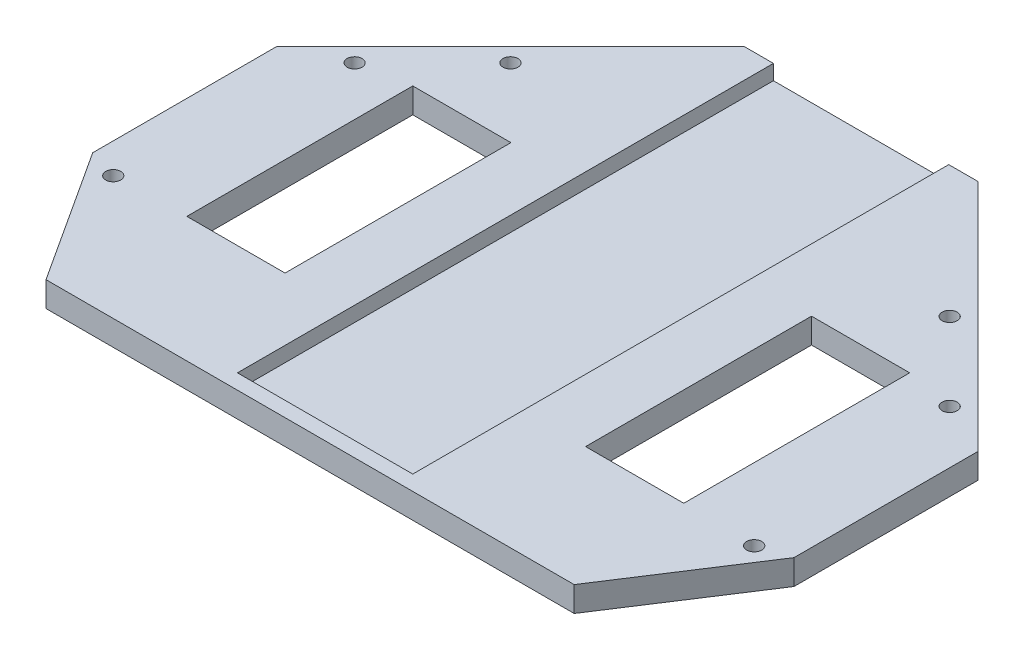
SolidWorks part; units mm, degrees
ref_plane "Front Plane" through (0, 0, 0) normal (0, 0, 1) x (1, 0, 0)
ref_plane "Top Plane" through (0, 0, 0) normal (0, 1, 0) x (1, 0, 0)
ref_plane "Right Plane" through (0, 0, 0) normal (1, 0, 0) x (0, 0, -1)
sketch "Sketch1" plane through (0, 0, 0) normal (0, 1, 0) x (1, 0, 0)
  line L0 (-52.7197, -40) -> (-70, -13.3906)
  line L1 (-70, -13.3906) -> (-70, 23.3381)
  line L2 (-70, 23.3381) -> (-23.3381, 70)
  line L4 (0, -40) -> (0, 70)
  line L5 (0, -40) -> (-52.7197, -40)
  line L6 (-59.397, 28.2843) -> (-43.8406, 43.8406) construction
  line L7 (-51.9976, -33.7676) -> (-63.9796, -15.3169) construction
  line L8 (-23.3381, 70) -> (0, 70)
  line L9 (0, 0) -> (-85, 0) construction
  line L10 (-43.8406, 43.8406) -> (0, 0) construction
  line L11 (-51.9976, -33.7676) -> (0, 0) construction
  line L12 (-49.6, 30.1) -> (-30, 30.1)
  line L13 (-49.6, 30.1) -> (-49.6, -15)
  line L14 (-49.6, -15) -> (-30, -15)
  line L15 (-30, 30.1) -> (-30, -15)
  circle A0 centre (0, 0) radius 85 construction
  circle A1 centre (-43.8406, 43.8406) radius 1.5
  circle A2 centre (-59.397, 28.2843) radius 1.5
  circle A4 centre (-63.9796, -15.3169) radius 1.5
  dimension "D7" = 3
  dimension "D17" = 170
  dimension "D3" = 4
  dimension "D5" = 40
  dimension "D6" = 70
  dimension "D8" = 62
  dimension "D9" = 22
  dimension "D10" = 22
  dimension "D11" = 19.6
  dimension "D12" = 45.1
  dimension "D13" = 30
  dimension "D14" = 45
  dimension "D15" = 33
  dimension "D16" = 15
  dimension "D18" = 4
  dimension "D19" = 70
extrude "Boss-Extrude1" add sketch "Sketch1" along normal blind 5
mirror "Mirror1" about plane through (0, 5, 40) normal (-1, 0, 0) of "Boss-Extrude1"
sketch "Sketch2" plane through (0, 5, 0) normal (0, 1, 0) x (1, 0, 0)
  line L0 (23.3381, 70) -> (-23.3381, 70) construction
  line L1 (-17.5, 70) -> (17.5, 70)
  line L2 (-17.5, 70) -> (-17.5, -37)
  line L3 (-17.5, -37) -> (17.5, -37)
  line L4 (17.5, 70) -> (17.5, -37)
  line L5 (-52.7197, -40) -> (52.7197, -40) construction
  dimension "D1" = 3
  dimension "D2" = 35
  dimension "D3" = 17.5
extrude "Cut-Extrude1" cut sketch "Sketch2" against normal blind 3
